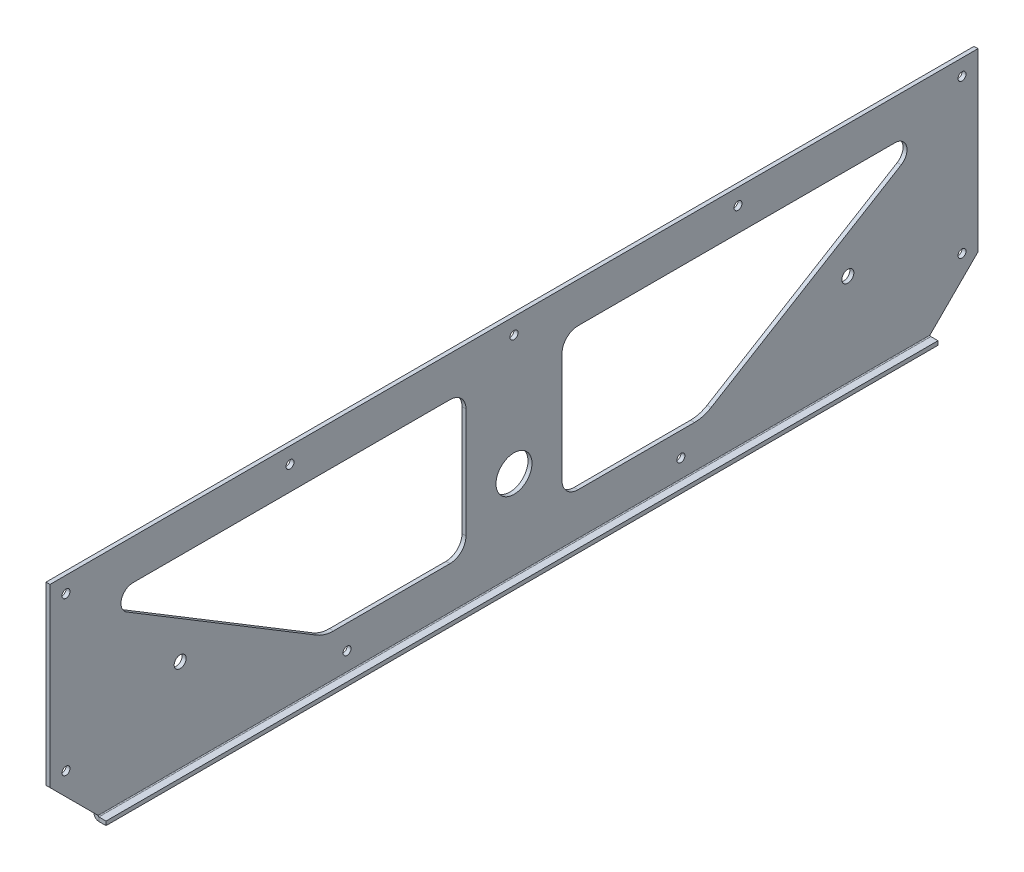
SolidWorks part; units mm, degrees
note: The reader was unsure of these and kept them because the rebuilt part matched: flange length of "Edge-Flange1".
material "6061-T6 (SS)"
ref_plane "Front Plane" through (0, 0, 0) normal (0, 0, 1) x (1, 0, 0)
ref_plane "Top Plane" through (0, 0, 0) normal (0, 1, 0) x (1, 0, 0)
ref_plane "Right Plane" through (0, 0, 0) normal (1, 0, 0) x (0, 0, -1)
sketch "Sketch1" plane through (0, 0, 0) normal (1, 0, 0) x (0, 0, -1)
  line L0 (330.2, 0) -> (-330.2, 0)
  line L1 (-330.2, 0) -> (-368.3, 38.1)
  line L2 (-368.3, 38.1) -> (-368.3, 177.8)
  line L3 (-368.3, 177.8) -> (368.3, 177.8)
  line L4 (368.3, 177.8) -> (368.3, 38.1)
  line L5 (368.3, 38.1) -> (330.2, 0)
  line L6 (-271.1374, -31.75) -> (271.1374, -31.75) construction
  point P4 (0, 0)
  point P17 (0, -31.75)
  dimension "D1" = 45
  dimension "D2" = 736.6
  dimension "D4" = 209.55
  dimension "D5" = 31.75
  dimension "D7" = 38.1
base flange "Base-Flange1" sketch "Sketch1" thickness 3.175 reverse thickness direction no parameters "D1"=0.7366
edge flange "Edge-Flange1" sketch "Sketch8" flange angle 90 flange length 6.35 flange position bend outside bend radius 0.7366 thickness 3.175 relief rectangular parameters "D6"=10
sketch "Sketch8" plane through (0, 0, 0) normal (0, 1, 0) x (0, 0, 1)
  line L0 (330.2, 0) -> (-330.2, 0) construction
  line L1 (330.2, 0) -> (-330.2, 0)
  line L2 (-330.2, 0) -> (-330.2, 6.35)
  line L3 (-330.2, 6.35) -> (330.2, 6.35)
  line L4 (330.2, 6.35) -> (330.2, 0)
bend "EdgeBend1" bend radius 0.7366 bend angle 90 parameters "D5"=1
sketch "Sketch9" plane through (0, 0, 0) normal (1, 0, 0) x (0, 0, -1)
  line L0 (-355.6, 177.8) -> (-355.6, 25.4) construction
  line L1 (368.3, 177.8) -> (-368.3, 177.8) construction
  line L2 (-368.3, 38.1) -> (-330.2, 0) construction
  line L3 (0, 0) -> (0, 177.8) construction
  line L4 (-355.6, 165.1) -> (355.6, 165.1) construction
  line L5 (355.6, 25.4) -> (355.6, 177.8) construction
  line L6 (-368.3, 177.8) -> (-368.3, 38.1) construction
  line L7 (330.2, 0) -> (368.3, 38.1) construction
  line L8 (-333.0278, -31.75) -> (182.8998, -31.75) construction
  line L9 (-330.2, 0) -> (330.2, 0) construction
  line L10 (-264.9792, 73.025) -> (0, 69.85) construction
  line L11 (0, 69.85) -> (264.9792, 73.025) construction
  line L12 (368.3, 177.8) -> (-368.3, 177.8) construction
  circle A0 centre (-355.6, 165.1) radius 3.175
  circle A1 centre (-355.6, 43.3605) radius 3.175
  circle A2 centre (-264.9792, 73.025) radius 101.6 construction
  circle A3 centre (-177.8, 165.1) radius 3.175
  circle A4 centre (0, 165.1) radius 3.175
  circle A5 centre (-132.4896, 14.2875) radius 3.175
  circle A6 centre (132.4896, 14.2875) radius 3.175
  circle A7 centre (0, 69.85) radius 38.1 construction
  circle A8 centre (177.8, 165.1) radius 3.175
  circle A9 centre (355.6, 165.1) radius 3.175
  circle A10 centre (264.9792, 73.025) radius 101.6 construction
  circle A14 centre (355.6, 43.3605) radius 3.175
  circle A15 centre (0, 69.85) radius 14.2875
  circle A16 centre (-264.9792, 73.025) radius 4.7625
  circle A17 centre (264.9792, 73.025) radius 4.7625
  circle A18 centre (0, 69.85) radius 101.6 construction
  point P26 (0, 165.1)
  point P41 (-132.4896, 71.4375)
  point P43 (132.4896, 71.4375)
  dimension "D3" = 203.2
  dimension "D4" = 6.35
  dimension "D10" = 28.575
  dimension "D13" = 9.525
  dimension "D14" = 9.525
  dimension "D11" = 264.9982
  dimension "D8" = 76.2
  dimension "D1" = 12.7
  dimension "D2" = 12.7
  dimension "D7" = 57.15
  dimension "D9" = 31.75
  dimension "D12" = 3.175
  dimension "D6" = 12.7
  dimension "D5" = 5
extrude "Cut-Extrude1" cut sketch "Sketch9" against normal through all normal cut yes
sketch "Sketch10" plane through (-3.175, 0, 0) normal (-1, 0, 0) x (0, 0, 1)
  line L0 (-302.4269, 146.05) -> (-50.8, 146.05)
  line L1 (-38.1, 133.35) -> (-38.1, 46.0375)
  line L2 (-50.8, 33.3375) -> (-143.2959, 33.3375)
  line L3 (-156.451, 37.0096) -> (-307.36, 128.377)
  line L4 (0, 165.1) -> (0, 69.85) construction
  line L5 (38.1, 133.35) -> (38.1, 46.0375)
  line L6 (302.4269, 146.05) -> (50.8, 146.05)
  line L7 (156.451, 37.0096) -> (307.36, 128.377)
  line L8 (50.8, 33.3375) -> (143.2959, 33.3375)
  circle A0 centre (-177.8, 165.1) radius 3.175 construction
  arc A1 (-302.4269, 146.05) -> (-307.36, 128.377) centre (-302.4269, 136.525) ccw
  arc A2 (-143.2959, 33.3375) -> (-156.451, 37.0096) centre (-143.2959, 58.7375) cw
  arc A3 (-50.8, 146.05) -> (-38.1, 133.35) centre (-50.8, 133.35) cw
  arc A4 (-38.1, 46.0375) -> (-50.8, 33.3375) centre (-50.8, 46.0375) cw
  arc A5 (38.1, 46.0375) -> (50.8, 33.3375) centre (50.8, 46.0375) ccw
  arc A6 (50.8, 146.05) -> (38.1, 133.35) centre (50.8, 133.35) ccw
  arc A7 (302.4269, 146.05) -> (307.36, 128.377) centre (302.4269, 136.525) cw
  arc A8 (143.2959, 33.3375) -> (156.451, 37.0096) centre (143.2959, 58.7375) ccw
  point P8 (-132.4896, 14.2875)
  point P9 (-177.8, 165.1)
  point P11 (-355.6, 165.1)
  point P16 (-264.9792, 73.025)
  point P19 (-336.55, 146.05)
  dimension "D6" = 9.525
  dimension "D7" = 25.4
  dimension "D8" = 12.7
  dimension "D1" = 38.1
  dimension "D2" = 19.05
  dimension "D3" = 19.05
  dimension "D4" = 25.4
  dimension "D5" = 19.05
extrude "Cut-Extrude2" cut sketch "Sketch10" against normal through all normal cut yes
sketch "Bend-Lines1" [suppressed] plane through (0, 0, 0) normal (0, 1, 0) x (1, 0, 0)
sketch "Bounding-Box1" [suppressed] plane through (0, 0, 0) normal (0, 1, 0) x (1, 0, 0)
sheet metal parameters "Sheet-Metal1" thickness 3.175 parameters "D1"=0.7366
flat pattern "Flat-Pattern1" [suppressed]
sketch "Bend-Lines2" plane through (0, 0, 0) normal (0, 1, 0) x (1, 0, 0)
sketch3d "Bounding-Box2" [suppressed]
  line L0 (374.65, 0, 0) -> (-374.65, 0, 0) construction
  line L1 (374.65, 558.8, 0) -> (-374.65, 558.8, 0) construction
  line L2 (374.65, 0, 0) -> (374.65, 558.8, 0) construction
  line L3 (-374.65, 0, 0) -> (-374.65, 558.8, 0) construction
sheet metal parameters "Sheet-Metal2" thickness 3.175 parameters "D1"=0.7366
flat pattern "Flat-Pattern1"
sketch "Bend-Lines2" plane through (0, 0, 0) normal (1, 0, 0) x (0, 0, -1)
  line L0 (-330.2, -1.8253) -> (330.2, -1.8253) construction
  line L1 (-330.2, -1.8253) -> (330.2, -1.8253) construction
sketch3d "Bounding-Box2" [suppressed]
  line L0 (368.3, -7.6766, 0) -> (-368.3, -7.6766, 0) construction
  line L1 (368.3, 488.95, 0) -> (-368.3, 488.95, 0) construction
  line L2 (368.3, -7.6766, 0) -> (368.3, 488.95, 0) construction
  line L3 (-368.3, -7.6766, 0) -> (-368.3, 488.95, 0) construction
bend of the flat pattern "Flatten-<EdgeBend1>1"
sheet metal parameters "Sheet-Metal3" thickness 3.175 parameters "D1"=0.7366
flat pattern "Flat-Pattern1"
sketch "Bend-Lines2" plane through (0, 0, 0) normal (1, 0, 0) x (0, 0, -1)
  line L0 (-330.2, -1.8253) -> (330.2, -1.8253) construction
  line L1 (-330.2, -1.8253) -> (330.2, -1.8253) construction
sketch3d "Bounding-Box2" [suppressed]
  line L0 (368.3, -9.2641, 0) -> (-368.3, -9.2641, 0) construction
  line L1 (368.3, 177.8, 0) -> (-368.3, 177.8, 0) construction
  line L2 (368.3, -9.2641, 0) -> (368.3, 177.8, 0) construction
  line L3 (-368.3, -9.2641, 0) -> (-368.3, 177.8, 0) construction
bend of the flat pattern "Flatten-<EdgeBend1>1"
sheet metal parameters "Sheet-Metal5" thickness 3.175 parameters "D1"=0.7366
flat pattern "Flat-Pattern1"
sketch "Bend-Lines2" plane through (0, 0, 0) normal (1, 0, 0) x (0, 0, -1)
  line L0 (-330.2, -1.8253) -> (330.2, -1.8253) construction
  line L1 (-330.2, -1.8253) -> (330.2, -1.8253) construction
sketch3d "Bounding-Box2" [suppressed]
  line L0 (368.3, -9.2641, 0) -> (-368.3, -9.2641, 0) construction
  line L1 (368.3, 177.8, 0) -> (-368.3, 177.8, 0) construction
  line L2 (368.3, -9.2641, 0) -> (368.3, 177.8, 0) construction
  line L3 (-368.3, -9.2641, 0) -> (-368.3, 177.8, 0) construction
bend of the flat pattern "Flatten-<EdgeBend1>1"
